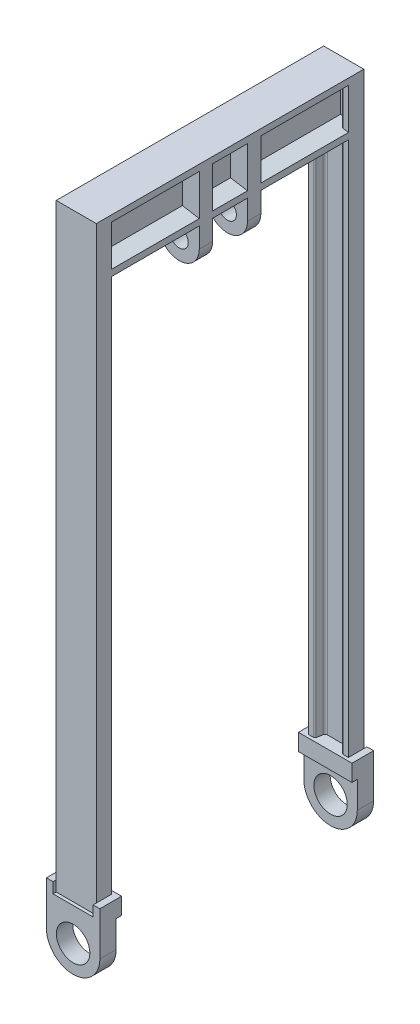
SolidWorks part; units mm, degrees
material "Custom Plastic"
ref_plane "Front Plane" through (0, 0, 0) normal (0, 0, 1) x (1, 0, 0)
ref_plane "Top Plane" through (0, 0, 0) normal (0, 1, 0) x (1, 0, 0)
ref_plane "Right Plane" through (0, 0, 0) normal (1, 0, 0) x (0, 0, -1)
sketch "Sketch1" plane through (0, 0, 0) normal (0, 1, 0) x (1, 0, 0)
  line L0 (-3.81, 25.4) -> (-3.81, 22.479)
  line L1 (-3.81, 25.4) -> (3.81, 25.4)
  line L2 (3.81, 25.4) -> (3.81, 22.479)
  line L3 (3.81, 22.479) -> (2.794, 22.479)
  line L4 (-3.81, 22.479) -> (-2.794, 22.479)
  line L5 (1.8522, 24.1939) -> (-1.8522, 24.1939)
  line L6 (2.3525, 23.7741) -> (2.5439, 22.6889)
  line L7 (-2.3525, 23.7741) -> (-2.5439, 22.6889)
  line L8 (-4.5183, 0) -> (4.2732, 0) construction
  line L9 (0, 25.4) -> (0, -25.4) construction
  line L10 (-2.2785, -24.1939) -> (-2.5439, -22.6889)
  line L11 (2.2785, -24.1939) -> (2.5439, -22.6889)
  line L12 (-2.1462, -24.2) -> (1.8606, -24.2)
  line L13 (-3.81, -22.479) -> (-2.794, -22.479)
  line L14 (3.81, -22.479) -> (2.794, -22.479)
  line L15 (3.81, -25.4) -> (3.81, -22.479)
  line L16 (-3.81, -25.4) -> (3.81, -25.4)
  line L17 (-3.81, -25.4) -> (-3.81, -22.479)
  arc A0 (-2.3525, 23.7741) -> (-1.8522, 24.1939) centre (-1.8522, 23.6859) cw
  arc A1 (1.8522, 24.1939) -> (2.3525, 23.7741) centre (1.8522, 23.6859) cw
  arc A2 (2.794, 22.479) -> (2.5439, 22.6889) centre (2.794, 22.733) cw
  arc A3 (-2.794, 22.479) -> (-2.5439, 22.6889) centre (-2.794, 22.733) ccw
  arc A4 (-2.794, -22.479) -> (-2.5439, -22.6889) centre (-2.794, -22.733) cw
  arc A5 (2.794, -22.479) -> (2.5439, -22.6889) centre (2.794, -22.733) ccw
  arc A6 (-2.1462, -24.2) -> (-2.2785, -24.1939) centre (-2.1891, -23.6938) cw
  arc A7 (1.8606, -24.2) -> (2.2785, -24.1939) centre (2.0628, -23.734) ccw
  point P8 (-2.2785, 24.1939)
  point P38 (2.2785, 24.1939)
  dimension "D7" = 0.254
  dimension "D8" = 0.254
  dimension "D6" = 0.508
  dimension "D1" = 7.62
  dimension "D2" = 2.921
  dimension "D4" = 10
  dimension "D5" = 10
  dimension "D9" = 1.016
  dimension "D10" = 1.016
  dimension "D11" = 25.4
  dimension "D3" = 1.2061
extrude "Boss-Extrude1" add sketch "Sketch1" along normal mid plane 114.3
sketch "Sketch2" plane through (0, 0, 25.4) normal (0, 0, 1) x (1, 0, 0)
  line L0 (-3.81, 57.15) -> (3.81, 57.15)
  line L1 (3.81, 57.15) -> (3.81, 55.95)
  line L2 (3.81, 57.15) -> (3.81, -57.15) construction
  line L3 (3.81, 55.95) -> (0.6, 55.4128)
  line L4 (0.6, 55.4128) -> (0.6, 48.7272)
  line L5 (0.6, 48.7272) -> (3.81, 48.19)
  line L6 (3.81, 48.19) -> (3.81, 46.99)
  line L7 (3.81, 46.99) -> (-3.81, 46.99)
  line L8 (-3.81, 57.15) -> (-3.81, -57.15) construction
  line L9 (-3.81, 46.99) -> (-3.81, 48.19)
  line L10 (-3.81, 48.19) -> (-0.6, 48.7272)
  line L11 (-0.6, 48.7272) -> (-0.6, 55.4128)
  line L12 (-0.6, 55.4128) -> (-3.81, 55.95)
  line L13 (-3.81, 55.95) -> (-3.81, 57.15)
  dimension "D1" = 10.16
  dimension "D2" = 1.2
  dimension "D3" = 1.2
  dimension "D4" = 1.2
  dimension "D5" = 9.5
extrude "Boss-Extrude2" add sketch "Sketch2" along direction (0, 0, 1) on the side against the normal up to surface (50.8 mm away) up to face at (0, 0, -25.4)
sketch "Sketch3" plane through (0, 0, 25.4) normal (0, 0, 1) x (1, 0, 0)
  line L0 (0, 0) -> (0, -74.6063) construction
  line L1 (-5.08, -54.61) -> (5.08, -54.61)
  line L2 (-5.08, -54.61) -> (-5.08, -62.865)
  line L4 (5.08, -54.61) -> (5.08, -62.865)
  line L5 (-3.81, -57.15) -> (3.81, -57.15) construction
  circle A0 centre (0, -62.865) radius 3.175
  arc A1 (-5.08, -62.865) -> (5.08, -62.865) centre (0, -62.865) ccw
  dimension "D3" = 6.35
  dimension "D1" = 10.16
  dimension "D2" = 2.54
  dimension "D4" = 5.715
extrude "Boss-Extrude3" add sketch "Sketch3" against normal offset from surface 0.6 and the other way blind 0.6 up to face at (-3.302, -5.08, 22.479) offset beyond the face yes
sketch "Sketch4" plane through (-5.08, 0, 0) normal (-1, 0, 0) x (0, 0, 1)
  line L0 (21.879, -62.865) -> (21.879, -54.61) construction
  line L1 (21.879, -57.785) -> (22.895, -57.785)
  line L2 (21.879, -57.785) -> (21.879, -67.945)
  line L3 (21.879, -67.945) -> (22.895, -67.945)
  line L4 (22.895, -57.785) -> (22.895, -67.945)
  line L5 (26, -62.865) -> (21.879, -62.865) construction
  dimension "D1" = 1.016
  dimension "D2" = 5.08
  dimension "D3" = 5.08
extrude "Cut-Extrude1" cut sketch "Sketch4" against normal through all
sketch "Sketch5" plane through (0, 0, 25.4) normal (0, 0, 1) x (1, 0, 0)
  line L0 (5.08, -54.61) -> (-5.08, -54.61) construction
  line L1 (-3.81, -54.61) -> (3.81, -54.61)
  line L2 (-3.81, -54.61) -> (-3.81, -56.61)
  line L3 (-3.81, -56.61) -> (3.81, -56.61)
  line L4 (3.81, -54.61) -> (3.81, -56.61)
  line L5 (-3.81, 57.15) -> (-3.81, -54.61) construction
  line L6 (3.81, -54.61) -> (3.81, 57.15) construction
  dimension "D1" = 2
extrude "Cut-Extrude2" cut sketch "Sketch5" along normal through all
sketch "Sketch6" plane through (0, 0, -25.4) normal (0, 0, -1) x (-1, 0, 0)
  line L0 (0, -11.9454) -> (0, -86.5517) construction
  line L1 (-5.08, -54.61) -> (5.08, -54.61)
  line L2 (-5.08, -54.61) -> (-5.08, -62.865)
  line L3 (5.08, -54.61) -> (5.08, -62.865)
  line L4 (-3.81, -57.15) -> (3.81, -57.15) construction
  circle A0 centre (0, -62.865) radius 3.175
  arc A1 (-5.08, -62.865) -> (5.08, -62.865) centre (0, -62.865) ccw
  dimension "D1" = 6.35
  dimension "D2" = 10.16
  dimension "D3" = 5.715
  dimension "D4" = 2.54
extrude "Boss-Extrude6" add sketch "Sketch6" against normal offset from surface 0.6 and the other way blind 0.6 up to face at (3.302, -5.08, -22.479) offset beyond the face yes
mirror "Mirror5" about plane through (0, 0, 0) normal (0, 0, 1) of "Cut-Extrude1"
mirror "Mirror6" about plane through (0, 0, 0) normal (0, 0, 1) of "Cut-Extrude2"
sketch "Sketch7" plane through (0, 0, 0) normal (0, 0, 1) x (1, 0, 0)
  line L0 (0, 43.18) -> (0, -5.7226) construction
  line L4 (3.81, 43.18) -> (3.81, 46.99)
  line L5 (3.81, 46.99) -> (-3.81, 46.99)
  line L6 (-3.81, 43.18) -> (-3.81, 46.99)
  line L7 (1.8606, 46.99) -> (-2.1462, 46.99) construction
  circle A0 centre (0, 43.18) radius 1.7145
  arc A1 (-3.81, 43.18) -> (3.81, 43.18) centre (0, 43.18) ccw
  point P6 (0, 43.18)
  point P8 (0, 43.5985)
  dimension "D1" = 3.429
  dimension "D3" = 7.62
extrude "Boss-Extrude7" add sketch "Sketch7" along normal blind 2.54 from offset 3.302
mirror "Mirror7" about plane through (0, 0, 0) normal (0, 0, 1) of "Boss-Extrude7"
sketch "Sketch8" plane through (-3.81, 0, 0) normal (-1, 0, 0) x (0, 0, 1)
  line L0 (-22.479, 55.95) -> (22.479, 55.95) construction
  line L1 (3.302, 55.95) -> (5.842, 55.95)
  line L2 (3.302, 55.95) -> (3.302, 48.19)
  line L3 (3.302, 48.19) -> (5.842, 48.19)
  line L4 (5.842, 55.95) -> (5.842, 48.19)
  line L5 (-22.479, 48.19) -> (22.479, 48.19) construction
  line L6 (5.842, 46.99) -> (5.842, 43.18) construction
  line L7 (3.302, 46.99) -> (3.302, 43.18) construction
extrude "Boss-Extrude8" add sketch "Sketch8" against normal up to surface (7.62 mm away) up to face at (3.81, 52.07, 0)
mirror "Mirror8" about plane through (0, 0, 0) normal (0, 0, 1) of "Boss-Extrude8"
equation "\"D10@Sketch1\"=\"D9@Sketch1\""
equation "\"D3@Sketch2\"=\"D2@Sketch2\""
equation "\"D8@Sketch1\"=\"D7@Sketch1\""
equation "\"D5@Sketch1\"=\"D4@Sketch1\""
